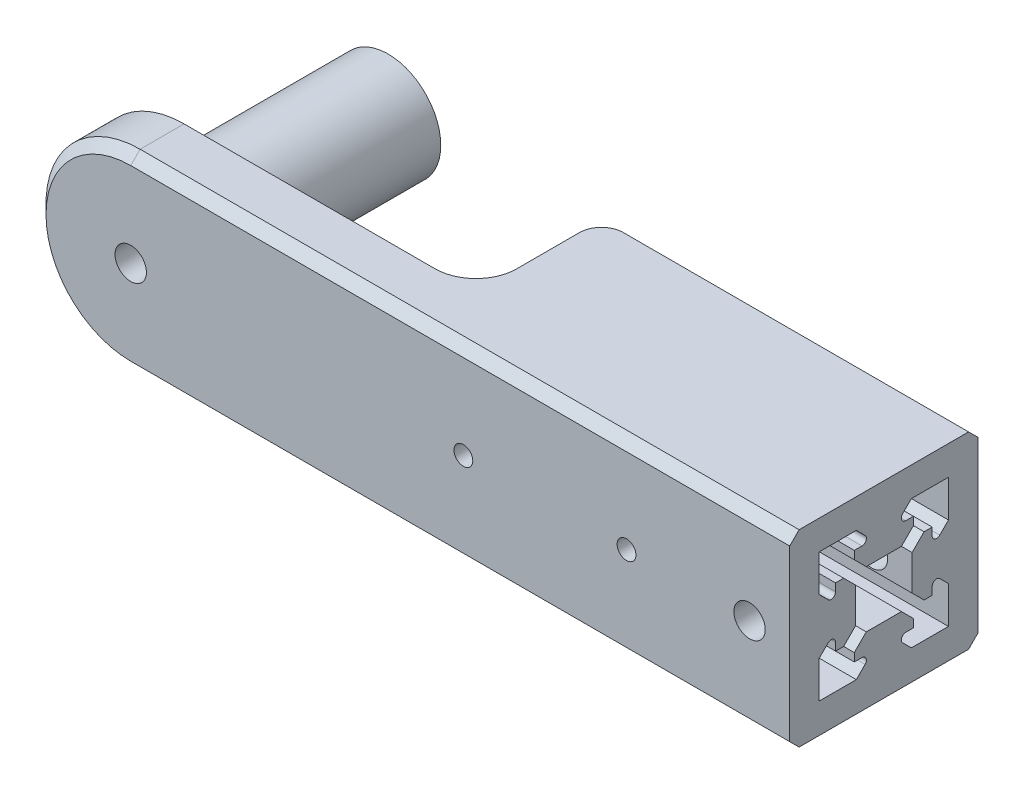
SolidWorks part; units mm, degrees
ref_plane "Front Plane" through (0, 0, 0) normal (0, 0, 1) x (1, 0, 0)
ref_plane "Top Plane" through (0, 0, 0) normal (0, 1, 0) x (1, 0, 0)
ref_plane "Right Plane" through (0, 0, 0) normal (1, 0, 0) x (0, 0, -1)
sketch "Sketch1" plane through (0, 0, 0) normal (0, 0, 1) x (1, 0, 0)
  circle A0 centre (0, 0) radius 8.4
  dimension "D1" = 16.8
extrude "Boss-Extrude1" add sketch "Sketch1" along normal blind 30
sketch "Sketch3" plane through (0, 0, 30) normal (0, 0, 1) x (1, 0, 0)
  circle A0 centre (0, 0) radius 10
  dimension "D1" = 20
extrude "Boss-Extrude2" add sketch "Sketch3" along normal blind 1
sketch "Sketch4" plane through (0, 0, 31) normal (0, 0, 1) x (1, 0, 0)
  line L0 (0, 15) -> (105, 15)
  line L1 (105, 15) -> (105, -15)
  line L2 (105, -15) -> (0, -15)
  arc A0 (0, 15) -> (0, -15) centre (0, 0) ccw
  dimension "D1" = 30
  dimension "D2" = 105
extrude "Boss-Extrude3" add sketch "Sketch4" along normal blind 10
sketch "Sketch5" plane through (0, 15, 0) normal (0, 1, 0) x (1, 0, 0)
  line L0 (40, -31) -> (105, -31)
  line L2 (105, -31) -> (105, -11)
  line L3 (105, -11) -> (50, -11)
  line L4 (45, -26) -> (45, -16)
  arc A0 (40, -31) -> (45, -26) centre (40, -26) ccw
  arc A1 (50, -11) -> (45, -16) centre (50, -16) ccw
  point P11 (45, -11)
  dimension "D3" = 5
  dimension "D4" = 5
  dimension "D1" = 60
  dimension "D2" = 20
extrude "Boss-Extrude4" add sketch "Sketch5" against normal blind 30
sketch "Sketch6" plane through (105, 0, 0) normal (1, 0, 0) x (0, 0, -1)
  line L0 (-23.1971, 4.5537) -> (-28.8029, 4.5537)
  line L1 (-28.8029, 4.5537) -> (-30.7101, 6.4608)
  line L2 (-30.7101, 6.4608) -> (-30.7101, 7.7537)
  line L3 (-30.7101, 7.7537) -> (-29.4828, 7.7537)
  line L4 (-28.9879, 8.9487) -> (-30.3879, 10.3487)
  line L5 (-36.295, 4.4416) -> (-34.895, 3.0416)
  line L6 (-33.7, 3.5366) -> (-33.7, 4.7638)
  line L7 (-33.7, 4.7638) -> (-32.4071, 4.7638)
  line L8 (-32.4071, 4.7638) -> (-30.5, 2.8567)
  line L9 (-30.5, 2.8567) -> (-30.5, -2.7492)
  line L10 (-30.5, -2.7492) -> (-32.4071, -4.6563)
  line L11 (-32.4071, -4.6563) -> (-33.7, -4.6563)
  line L12 (-33.7, -4.6563) -> (-33.7, -3.4291)
  line L13 (-34.895, -2.9342) -> (-36.295, -4.3342)
  line L14 (-30.3879, -10.2413) -> (-28.9879, -8.8413)
  line L15 (-29.4828, -7.6463) -> (-30.7101, -7.6463)
  line L16 (-30.7101, -7.6463) -> (-30.7101, -6.3534)
  line L17 (-30.7101, -6.3534) -> (-28.8029, -4.4463)
  line L18 (-28.8029, -4.4463) -> (-23.1971, -4.4463)
  line L19 (-30.3879, -10.2413) -> (-36.295, -10.2413)
  line L20 (-36.295, -10.2413) -> (-36.295, -4.3342)
  line L21 (-36.295, 4.4416) -> (-36.295, 10.3487)
  line L22 (-36.295, 10.3487) -> (-30.3879, 10.3487)
  line L23 (-26, 15.3277) -> (-26, -14.6723) construction
  line L24 (-15.705, 10.3487) -> (-21.6121, 10.3487)
  line L25 (-15.705, 4.4416) -> (-15.705, 10.3487)
  line L26 (-15.705, -10.2413) -> (-15.705, -4.3342)
  line L27 (-21.6121, -10.2413) -> (-15.705, -10.2413)
  line L28 (-21.2899, -6.3534) -> (-23.1971, -4.4463)
  line L29 (-21.2899, -7.6463) -> (-21.2899, -6.3534)
  line L30 (-22.5172, -7.6463) -> (-21.2899, -7.6463)
  line L31 (-21.6121, -10.2413) -> (-23.0121, -8.8413)
  line L32 (-17.105, -2.9342) -> (-15.705, -4.3342)
  line L33 (-18.3, -4.6563) -> (-18.3, -3.4291)
  line L34 (-19.5929, -4.6563) -> (-18.3, -4.6563)
  line L35 (-21.5, -2.7492) -> (-19.5929, -4.6563)
  line L36 (-21.5, 2.8567) -> (-21.5, -2.7492)
  line L37 (-19.5929, 4.7638) -> (-21.5, 2.8567)
  line L38 (-18.3, 4.7638) -> (-19.5929, 4.7638)
  line L39 (-18.3, 3.5366) -> (-18.3, 4.7638)
  line L40 (-15.705, 4.4416) -> (-17.105, 3.0416)
  line L41 (-23.0121, 8.9487) -> (-21.6121, 10.3487)
  line L42 (-21.2899, 7.7537) -> (-22.5172, 7.7537)
  line L43 (-21.2899, 6.4608) -> (-21.2899, 7.7537)
  line L44 (-23.1971, 4.5537) -> (-21.2899, 6.4608)
  line L45 (-41, 15) -> (-11, 15) construction
  arc A0 (-23.0121, -8.8413) -> (-22.5172, -7.6463) centre (-22.5172, -8.3463) cw
  arc A1 (-29.4828, 7.7537) -> (-28.9879, 8.9487) centre (-29.4828, 8.4537) ccw
  arc A2 (-18.3, -3.4291) -> (-17.105, -2.9342) centre (-17.6, -3.4291) cw
  arc A3 (-17.105, 3.0416) -> (-18.3, 3.5366) centre (-17.6, 3.5366) cw
  arc A4 (-34.895, 3.0416) -> (-33.7, 3.5366) centre (-34.4, 3.5366) ccw
  arc A5 (-33.7, -3.4291) -> (-34.895, -2.9342) centre (-34.4, -3.4291) ccw
  arc A6 (-22.5172, 7.7537) -> (-23.0121, 8.9487) centre (-22.5172, 8.4537) cw
  arc A7 (-28.9879, -8.8413) -> (-29.4828, -7.6463) centre (-29.4828, -8.3463) ccw
  point P66 (-26, 15)
  dimension "D7" = 0.7
  dimension "D16" = 0.7
  dimension "D31" = 0.7
  dimension "D1" = 5.6059
  dimension "D2" = 2.6971
  dimension "D3" = 1.2929
  dimension "D4" = 2.595
  dimension "D5" = 135
  dimension "D6" = 1.2934
  dimension "D8" = 1.9799
  dimension "D9" = 135
  dimension "D10" = 1.2272
  dimension "D11" = 5.6059
  dimension "D12" = 2.6971
  dimension "D13" = 1.2929
  dimension "D14" = 1.2272
  dimension "D15" = 1.2934
  dimension "D17" = 1.9799
  dimension "D18" = 225
  dimension "D19" = 5.9071
  dimension "D20" = 135
  dimension "D21" = 90
  dimension "D22" = 135
  dimension "D23" = 2.595
  dimension "D24" = 135
  dimension "D25" = 135
  dimension "D26" = 1.2934
  dimension "D27" = 5.9071
  dimension "D28" = 1.9799
  dimension "D29" = 135
  dimension "D30" = 1.2934
  dimension "D32" = 1.2272
  dimension "D33" = 90
  dimension "D34" = 135
  dimension "D35" = 1.2929
  dimension "D36" = 2.595
  dimension "D37" = 2.6971
  dimension "D38" = 5.6059
  dimension "D39" = 5.9071
extrude "Cut-Extrude1" cut sketch "Sketch6" against normal blind 66
chamfer "Chamfer1" distance 1.5 angle 45 14 edges at (77.5, -15, 11) (46.4645, -15, 12.4645) (45, -15, 21) (43.5355, -15, 29.5355) (20, -15, 31) (-15, 0, 31) (20, 15, 31) (43.5355, 15, 29.5355) (45, 15, 21) (46.4645, 15, 12.4645) (77.5, 15, 11) (52.5, -15, 41) (-15, 0, 41) (52.5, 15, 41)
sketch "Sketch7" plane through (0, 0, 41) normal (0, 0, 1) x (1, 0, 0)
  line L0 (105, -13.5) -> (105, 13.5) construction
  circle A0 centre (53, 0) radius 1.5
  circle A1 centre (79, 0) radius 1.5
  circle A2 centre (98.6, 0) radius 2.5
  circle A3 centre (0, 0) radius 2.5
  dimension "D4" = 5
  dimension "D5" = 3
  dimension "D6" = 5
  dimension "D7" = 3
  dimension "D1" = 52
  dimension "D2" = 26
  dimension "D3" = 19.6
extrude "Cut-Extrude2" cut sketch "Sketch7" against normal through all
